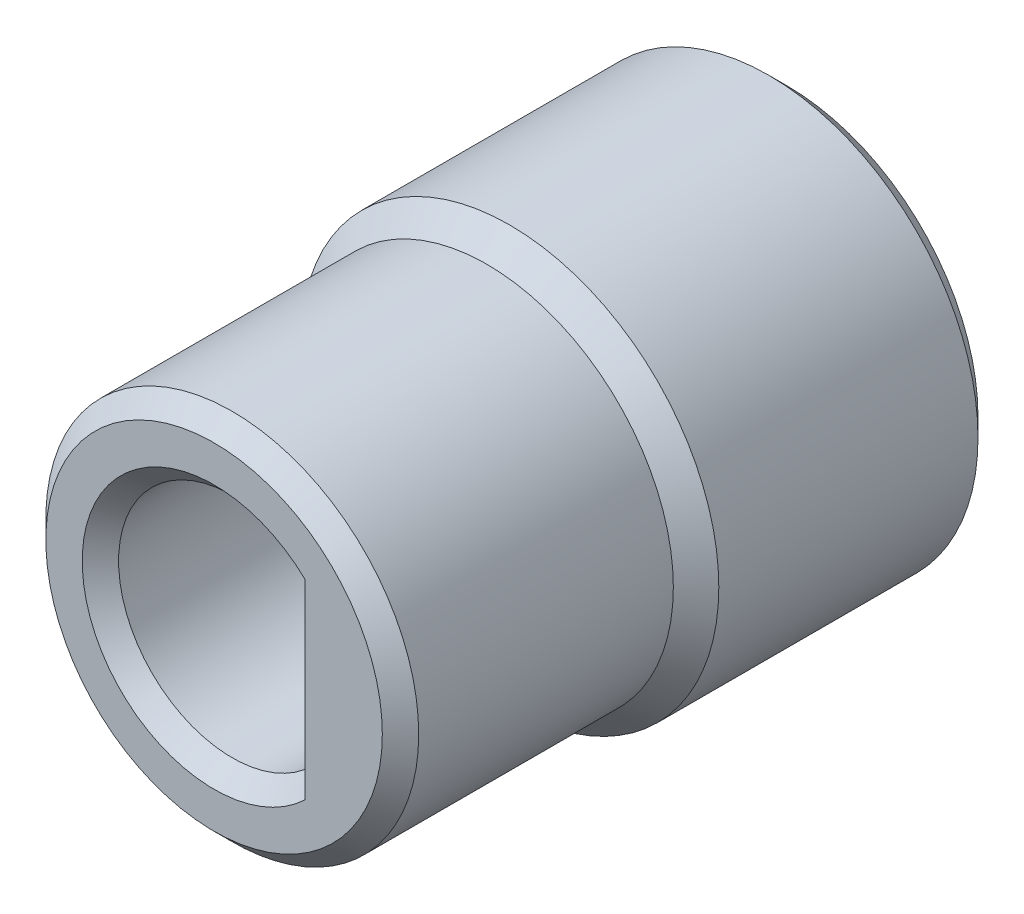
SolidWorks part; units mm, degrees
ref_plane "Front Plane" through (0, 0, 0) normal (0, 0, 1) x (1, 0, 0)
ref_plane "Top Plane" through (0, 0, 0) normal (0, 1, 0) x (1, 0, 0)
ref_plane "Right Plane" through (0, 0, 0) normal (1, 0, 0) x (0, 0, -1)
sketch "Sketch1" plane through (0, 0, 0) normal (0, 0, 1) x (1, 0, 0)
  circle A0 centre (0, 0) radius 3
  circle A1 centre (0, 0) radius 4.6
  dimension "D1" = 1.6
  dimension "D2" = 6
extrude "Boss-Extrude1" add sketch "Sketch1" along normal blind 6.6
sketch "Sketch2" plane through (0, 0, 6.6) normal (0, 0, 1) x (1, 0, 0)
  line L1 (1.6, -1.9209) -> (1.6, 1.9209)
  line L2 (0, 3) -> (0, 4.6) construction
  line L3 (-2.5, 0) -> (-4.1, 0) construction
  arc A1 (1.6, 1.9209) -> (1.6, -1.9209) centre (0, 0) ccw
  circle A3 centre (0, 0) radius 4.1
  circle A4 centre (0, 0) radius 3 construction
  circle A5 centre (0, 0) radius 4.6 construction
  dimension "D1" = 2.5
  dimension "D2" = 4.1
extrude "Boss-Extrude2" add sketch "Sketch2" along normal blind 6
chamfer "Chamfer2" distance 0.5 angle 45 1 edges at (4.6, 0, 6.6)
chamfer "Chamfer3" distance 0.4 angle 45 3 edges at (-2.5, 0, 12.6) (1.6, 0, 12.6) (3, 0, 0)
chamfer "Chamfer4" distance 0.4 distance2 0.8 1 edges at (3, 0, 6.6) first distance on face at (3, 0, 6.6)
chamfer "Chamfer5" distance 0.4 angle 45 2 edges at (4.6, 0, 0) (4.1, 0, 12.6)
